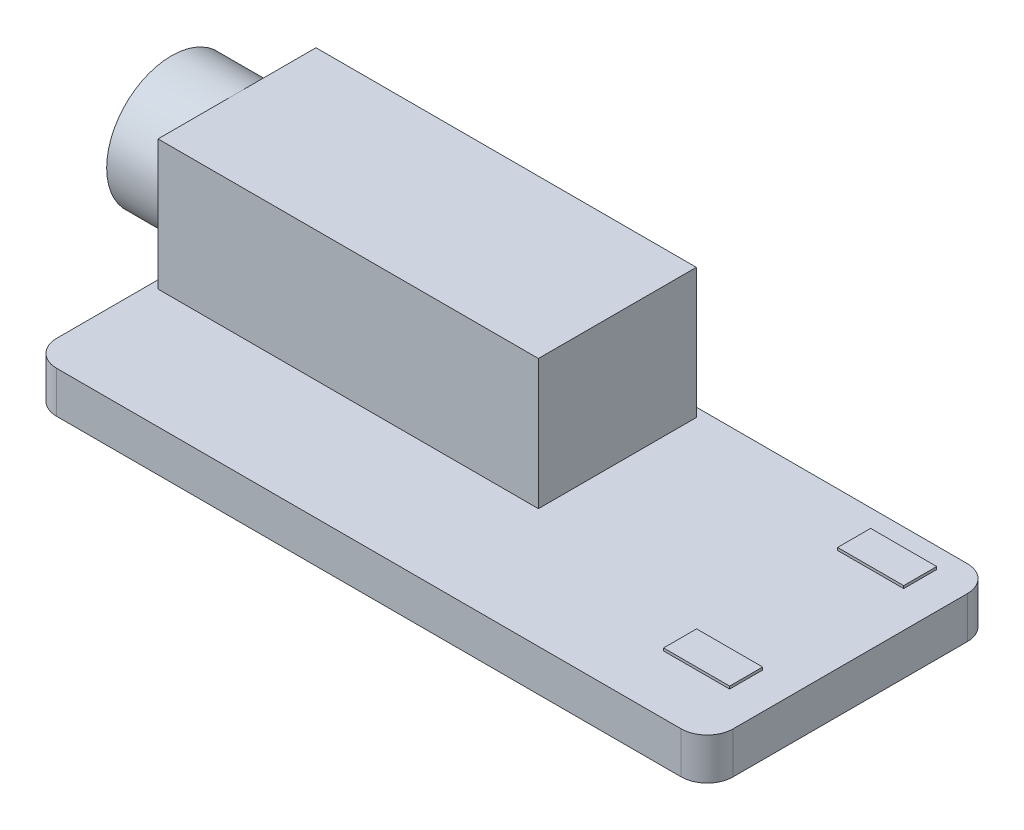
SolidWorks part; units mm, degrees
ref_plane "Front Plane" through (0, 0, 0) normal (0, 0, 1) x (1, 0, 0)
ref_plane "Top Plane" through (0, 0, 0) normal (0, 1, 0) x (1, 0, 0)
ref_plane "Right Plane" through (0, 0, 0) normal (1, 0, 0) x (0, 0, -1)
sketch "Sketch1" plane through (0, 0, 0) normal (0, 1, 0) x (1, 0, 0)
  line L1 (12, 5.5) -> (-12, 5.5)
  line L2 (13, 4.5) -> (13, -4.5)
  line L3 (12, -5.5) -> (-12, -5.5)
  line L4 (-13, 4.5) -> (-13, -4.5)
  line L5 (13, 5.5) -> (-13, -5.5) construction
  line L6 (13, -5.5) -> (-13, 5.5) construction
  arc A0 (12, 5.5) -> (13, 4.5) centre (12, 4.5) cw
  arc A1 (13, -4.5) -> (12, -5.5) centre (12, -4.5) cw
  arc A2 (-12, -5.5) -> (-13, -4.5) centre (-12, -4.5) cw
  arc A3 (-12, 5.5) -> (-13, 4.5) centre (-12, 4.5) ccw
  point P0 (0, 0)
  dimension "D3" = 1
  dimension "D1" = 26
  dimension "D2" = 11
extrude "Boss-Extrude1" add sketch "Sketch1" along normal blind 1.6
sketch "Sketch2" plane through (0, 1.6, 0) normal (0, 1, 0) x (1, 0, 0)
  line L0 (-13, -4.5) -> (-13, -5.5) construction
  line L1 (9.07, 4.715) -> (11.61, 4.715)
  line L2 (9.07, 4.715) -> (9.07, 3.445)
  line L3 (9.07, 3.445) -> (11.61, 3.445)
  line L4 (11.61, 4.715) -> (11.61, 3.445)
  line L5 (9.07, 4.715) -> (11.61, 3.445) construction
  line L6 (9.07, 3.445) -> (11.61, 4.715) construction
  line L7 (9.07, -1.975) -> (11.61, -1.975)
  line L8 (9.07, -1.975) -> (9.07, -3.245)
  line L9 (9.07, -3.245) -> (11.61, -3.245)
  line L10 (11.61, -1.975) -> (11.61, -3.245)
  line L11 (9.07, -1.975) -> (11.61, -3.245) construction
  line L12 (9.07, -3.245) -> (11.61, -1.975) construction
  line L13 (-13, -5.5) -> (-12, -5.5) construction
  line L14 (-12, -5.5) -> (12, -5.5) construction
  point P0 (10.34, 4.08)
  point P5 (10.34, -2.61)
  dimension "D1" = 2.54
  dimension "D2" = 1.27
  dimension "D3" = 23.34
  dimension "D4" = 2.89
  dimension "D5" = 9.58
extrude "Boss-Extrude2" add sketch "Sketch2" along normal blind 0.1
sketch "Sketch3" plane through (0, 1.6, 0) normal (0, 1, 0) x (1, 0, 0)
  line L0 (-13, 4.5) -> (-13, -4.5) construction
  line L1 (-12.69, 5.155) -> (1.93, 5.155)
  line L2 (-12.69, 5.155) -> (-12.69, -0.915)
  line L3 (-12.69, -0.915) -> (1.93, -0.915)
  line L4 (1.93, 5.155) -> (1.93, -0.915)
  line L5 (-12.69, 5.155) -> (1.93, -0.915) construction
  line L6 (-12.69, -0.915) -> (1.93, 5.155) construction
  line L7 (-12, -5.5) -> (12, -5.5) construction
  point P0 (-5.38, 2.12)
  dimension "D1" = 14.62
  dimension "D2" = 6.07
  dimension "D3" = 7.62
  dimension "D4" = 7.62
extrude "Boss-Extrude3" add sketch "Sketch3" along normal blind 5
sketch "Sketch4" plane through (-12.69, 0, 0) normal (-1, 0, 0) x (0, 0, 1)
  line L0 (-5.155, 4.1) -> (0.915, 4.1) construction
  line L1 (-5.155, 6.6) -> (-5.155, 1.6) construction
  line L2 (0.915, 6.6) -> (0.915, 1.6) construction
  circle A0 centre (-2.12, 4.1) radius 2.49
  circle A1 centre (-2.12, 4.1) radius 1.795
  point P9 (-2.12, 4.1)
  dimension "D1" = 3.59
  dimension "D2" = 4.98
extrude "Boss-Extrude5" add sketch "Sketch4" along normal blind 2.52
